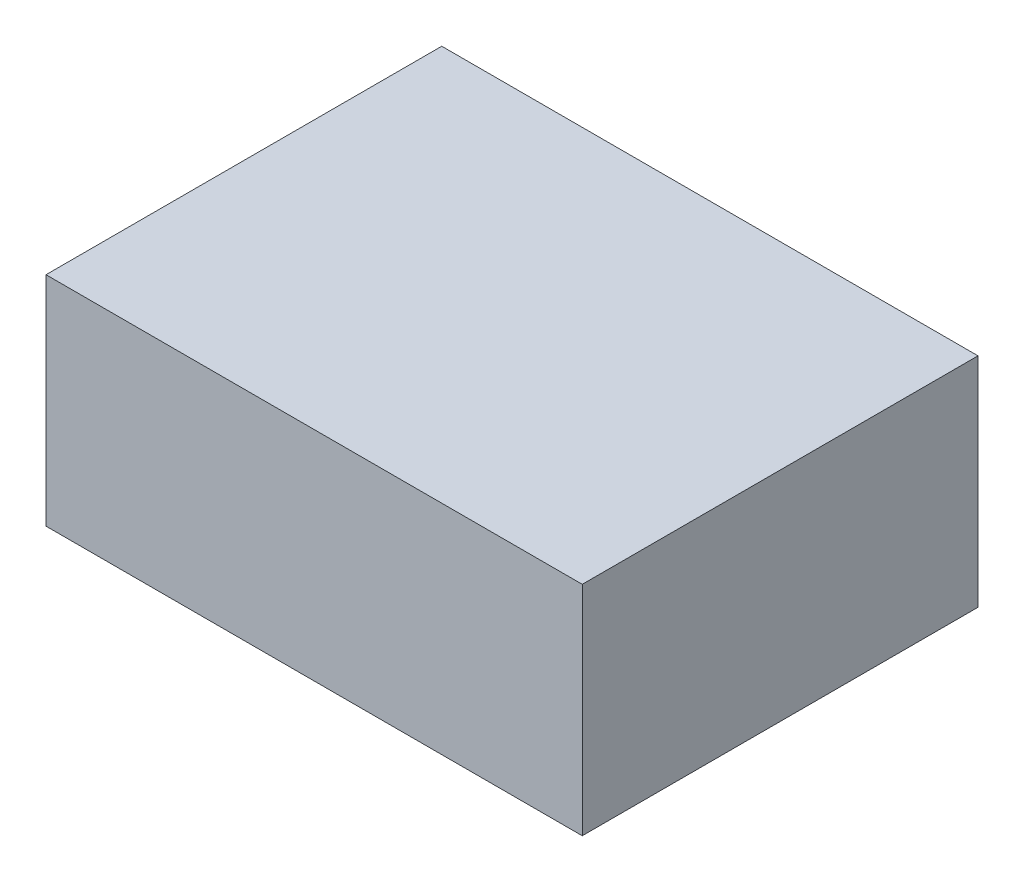
SolidWorks part; units mm, degrees
ref_plane "Front Plane" through (0, 0, 0) normal (0, 0, 1) x (1, 0, 0)
ref_plane "Top Plane" through (0, 0, 0) normal (0, 1, 0) x (1, 0, 0)
ref_plane "Right Plane" through (0, 0, 0) normal (1, 0, 0) x (0, 0, -1)
sketch "Sketch1" plane through (0, 0, 0) normal (0, 1, 0) x (1, 0, 0)
  line L1 (0, 0) -> (114.5, 0)
  line L2 (0, 0) -> (0, 84.5)
  line L3 (0, 84.5) -> (114.5, 84.5)
  line L4 (114.5, 0) -> (114.5, 84.5)
  dimension "D1" = 114.5
  dimension "D2" = 84.5
extrude "Boss-Extrude3" add sketch "Sketch1" along normal blind 46.5
